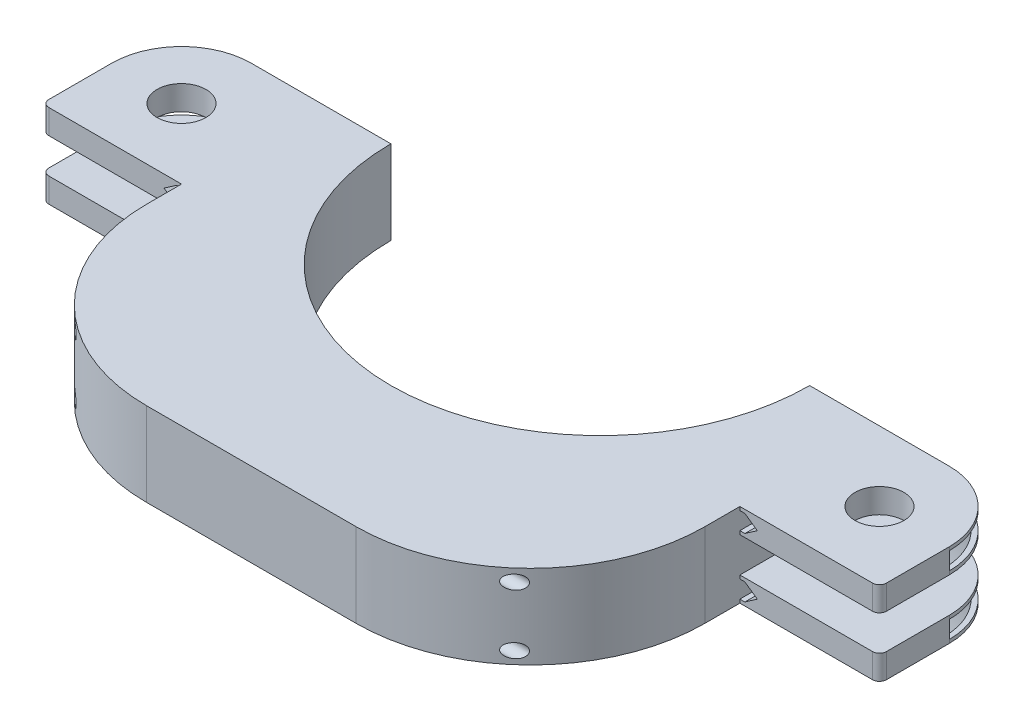
SolidWorks part; units mm, degrees
ref_plane "Front Plane" through (0, 0, 0) normal (0, 0, 1) x (1, 0, 0)
ref_plane "Top Plane" through (0, 0, 0) normal (0, 1, 0) x (1, 0, 0)
ref_plane "Right Plane" through (0, 0, 0) normal (1, 0, 0) x (0, 0, -1)
sketch "Sketch3" plane through (0, 0, 0) normal (0, 1, 0) x (1, 0, 0)
  line L0 (-3.2653, 27.8512) -> (-3.2653, -14.7845) construction
  line L1 (-23.2653, 15.6122) -> (16.7347, 15.6122)
  line L3 (-10.7653, -9.3878) -> (4.2347, -9.3878)
  line L4 (16.7347, 5.6122) -> (16.7347, 3.1122)
  line L5 (16.7347, 15.6122) -> (21.7347, 15.6122)
  line L7 (16.7347, 5.6122) -> (26.2347, 5.6122)
  line L8 (26.7347, 10.6122) -> (26.7347, 6.1122)
  line L9 (-33.2653, 10.6122) -> (-33.2653, 6.1122)
  line L10 (-23.2653, 5.6122) -> (-32.7653, 5.6122)
  line L11 (-23.2653, 15.6122) -> (-28.2653, 15.6122)
  line L12 (-23.2653, 5.6122) -> (-23.2653, 3.1122)
  circle A0 centre (21.7347, 10.6122) radius 1.75
  arc A1 (21.7347, 15.6122) -> (26.7347, 10.6122) centre (21.7347, 10.6122) cw
  arc A2 (26.2347, 5.6122) -> (26.7347, 6.1122) centre (26.2347, 6.1122) ccw
  arc A3 (4.2347, -9.3878) -> (16.7347, 3.1122) centre (4.2347, 3.1122) ccw
  arc A4 (-10.7653, -9.3878) -> (-23.2653, 3.1122) centre (-10.7653, 3.1122) cw
  arc A5 (-32.7653, 5.6122) -> (-33.2653, 6.1122) centre (-32.7653, 6.1122) cw
  arc A6 (-28.2653, 15.6122) -> (-33.2653, 10.6122) centre (-28.2653, 10.6122) ccw
  circle A7 centre (-28.2653, 10.6122) radius 1.75
  point P0 (-3.2653, 15.6122)
  point P28 (-3.2653, -9.3878)
  dimension "D5" = 3.5
  dimension "D3" = 0.5
  dimension "D2" = 12.5
  dimension "D1" = 20
  dimension "D6" = 5
  dimension "D7" = 5
extrude "Boss-Extrude1" add sketch "Sketch3" along normal blind 6
sketch "Sketch4" plane through (0, 0, -15.6122) normal (0, 0, -1) x (-1, 0, 0)
  line L0 (-21.7347, 6) -> (28.2653, 6) construction
  line L5 (3.2653, 6) -> (3.2653, 0) construction
  line L6 (-21.7347, 0) -> (28.2653, 0) construction
  line L7 (-21.7347, 3) -> (28.2653, 3) construction
  line L8 (-21.7347, 6) -> (-21.7347, 0) construction
  line L9 (28.2653, 6) -> (28.2653, 0) construction
  line L10 (33.2653, 1.75) -> (23.2653, 1.75)
  line L11 (-26.7347, 4.25) -> (-16.7347, 4.25)
  line L12 (-26.7347, 4.25) -> (-26.7347, 1.75)
  line L13 (-26.7347, 1.75) -> (-16.7347, 1.75)
  line L14 (-16.7347, 4.25) -> (-16.7347, 1.75)
  line L15 (23.2653, 4.25) -> (23.2653, 1.75)
  line L16 (33.2653, 4.25) -> (23.2653, 4.25)
  line L17 (33.2653, 4.25) -> (33.2653, 1.75)
  dimension "D1" = 1.25
  dimension "D2" = 2.5
  dimension "D3" = 20
  dimension "D4" = 10
extrude "Cut-Extrude1" cut sketch "Sketch4" against normal blind 10
ref_axis "Axis1" through (-28.2653, 1.75, -10.6122) along (0, -1, 0)
ref_plane "Plane1" through (0, 0, -10.6122) normal (0, 0, 1) x (1, 0, 0)
sketch "Sketch7" plane through (0, 0, -10.6122) normal (0, 0, 1) x (1, 0, 0)
  line L0 (-28.2653, 1.75) -> (-28.2653, 0) construction
  line L1 (-28.2653, 1.7467) -> (-33.2653, 1.7467) construction
  line L2 (-28.2653, 1.7467) -> (-28.2653, 0) construction
  line L3 (-28.2653, 0) -> (-33.2653, 0) construction
  line L4 (-33.2653, 1.7467) -> (-33.2653, 0) construction
  line L5 (-33.2653, 0) -> (-32.7653, 0) construction
  line L6 (-33.2653, 0) -> (-28.2653, 0) construction
  line L7 (-33.2653, 1.7467) -> (-28.2653, 0) construction
  line L8 (-28.2653, 1.7467) -> (-33.2653, 0) construction
  line L9 (-30.7653, 0) -> (-30.7653, 1.7467) construction
  line L10 (-32.9075, 0.25) -> (-30.7653, 1.7467) construction
  line L11 (-32.9075, 1.4967) -> (-30.7653, 0) construction
  line L13 (-33.2653, 1.7467) -> (-33.2653, 0) construction
  line L15 (-33.2653, 1.4967) -> (-32.9075, 1.4967)
  line L16 (-28.2653, 0.8733) -> (-33.2653, 0.8733) construction
  line L17 (-33.2653, 1.4967) -> (-33.2653, 0.25)
  line L18 (-33.2653, 0.25) -> (-32.9075, 0.25)
  line L19 (-32.9075, 0.25) -> (-32.0153, 0.8733)
  line L20 (-32.0153, 0.8733) -> (-32.9075, 1.4967)
  dimension "D1" = 5
  dimension "D2" = 0.25
revolve "Cut-Revolve1" cut sketch "Sketch7" angle 180 about L2
sketch "Sketch9" plane through (0, 0, -5.6122) normal (0, 0, 1) x (1, 0, 0)
  line L1 (-28.2653, 1.75) -> (-33.2653, 1.75) construction
  line L2 (-28.2653, 1.75) -> (-28.2653, 0.0033) construction
  line L3 (-28.2653, 0.0033) -> (-33.2653, 0.0033) construction
  line L4 (-33.2653, 1.75) -> (-33.2653, 0.0033) construction
  line L7 (-33.2653, 1.75) -> (-28.2653, 0.0033) construction
  line L8 (-28.2653, 1.75) -> (-33.2653, 0.0033) construction
  line L9 (-30.7653, 0.0033) -> (-30.7653, 1.75) construction
  line L10 (-32.9075, 0.2533) -> (-30.7653, 1.75) construction
  line L11 (-32.9075, 1.5) -> (-30.7653, 0.0033) construction
  line L13 (-33.2653, 1.75) -> (-33.2653, 0.0033) construction
  line L15 (-33.2653, 1.5) -> (-32.9075, 1.5) construction
  line L16 (-28.2653, 0.8767) -> (-33.2653, 0.8767) construction
  line L17 (-33.2653, 1.5) -> (-33.2653, 0.2533) construction
  line L18 (-33.2653, 0.2533) -> (-32.9075, 0.2533) construction
  line L19 (-32.9075, 0.2533) -> (-32.0153, 0.8767) construction
  line L20 (-32.0153, 0.8767) -> (-32.9075, 1.5) construction
  line L21 (-28.2653, 1.75) -> (-28.2653, 0) construction
  line L22 (-23.2653, 1.75) -> (-32.7653, 1.75) construction
  line L23 (-23.6231, 0.2533) -> (-24.5153, 0.8767)
  line L24 (-23.2653, 0.2533) -> (-23.6231, 0.2533)
  line L25 (-23.2653, 1.5) -> (-23.2653, 0.2533)
  line L26 (-23.2653, 1.5) -> (-23.6231, 1.5)
  line L27 (-24.5153, 0.8767) -> (-23.6231, 1.5)
  dimension "D1" = 5
  dimension "D2" = 0.25
  dimension "D3" = 0
  dimension "D4" = 0
extrude "Cut-Extrude2" cut sketch "Sketch9" against normal blind 5
sketch "Sketch10" plane through (-23.2653, 0, 0) normal (-1, 0, 0) x (0, 0, 1)
  line L0 (-5.6122, 1.75) -> (9.3878, 1.75) construction
  line L5 (-3.1122, 6) -> (9.3878, 6) construction
  line L6 (-3.1122, 6) -> (-3.1122, 0) construction
  line L7 (-3.1122, 0) -> (9.3878, 0) construction
  line L8 (9.3878, 6) -> (9.3878, 0) construction
  line L9 (-3.1122, 1.75) -> (9.3878, 0) construction
  line L10 (-3.1122, 0) -> (9.3878, 1.75) construction
  line L11 (3.1378, 0.875) -> (3.1378, 1.75) construction
  line L12 (3.1378, 1.75) -> (9.3878, 0) construction
  line L13 (3.1378, 0.875) -> (3.1378, 0) construction
  line L14 (3.1378, 0) -> (9.3878, 1.75) construction
  circle A0 centre (6.2628, 0.875) radius 0.5
extrude "Cut-Extrude3" cut sketch "Sketch10" against normal blind 40
ref_plane "Plane2" through (0, 3, 0) normal (0, 1, 0) x (1, 0, 0)
ref_plane "Plane3" through (-3.2653, 0, 0) normal (-1, 0, 0) x (0, 0, 1)
mirror "Mirror5" about plane through (-3.2653, 0, 0) normal (-1, 0, 0) of "Cut-Extrude2", "Cut-Revolve1"
mirror "Mirror6" about plane through (0, 3, 0) normal (0, 1, 0) of "Cut-Revolve1", "Cut-Extrude2", "Cut-Extrude3", "Mirror5"
sketch "Sketch11" plane through (0, 0, 0) normal (0, -1, 0) x (1, 0, 0)
  line L0 (-3.2653, -15.6122) -> (-3.2653, 9.3878) construction
  line L1 (21.7347, -15.6122) -> (-28.2653, -15.6122) construction
  line L2 (-10.7653, 9.3878) -> (4.2347, 9.3878) construction
  line L3 (11.7347, -15.6122) -> (-18.2653, -15.6122)
  arc A0 (11.7347, -15.6122) -> (-18.2653, -15.6122) centre (-3.2653, -15.6122) ccw
extrude "Cut-Extrude4" cut sketch "Sketch11" against normal blind 6
